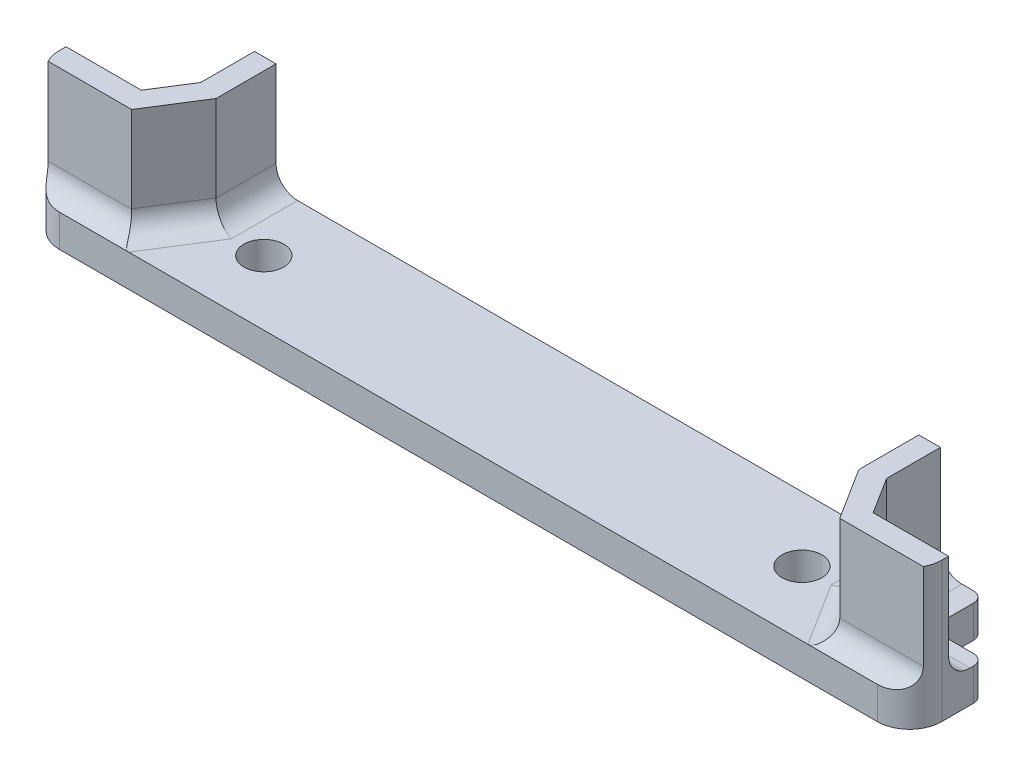
SolidWorks part; units mm, degrees
ref_plane "Front Plane" through (0, 0, 0) normal (0, 0, 1) x (1, 0, 0)
ref_plane "Top Plane" through (0, 0, 0) normal (0, 1, 0) x (1, 0, 0)
ref_plane "Right Plane" through (0, 0, 0) normal (1, 0, 0) x (0, 0, -1)
sketch "Sketch1" plane through (0, 0, 0) normal (0, 1, 0) x (1, 0, 0)
  line L1 (41, -6) -> (-41, -6)
  line L2 (41, -6) -> (41, 6)
  line L3 (41, 6) -> (-41, 6)
  line L4 (-41, -6) -> (-41, 6)
  line L5 (41, -6) -> (-41, 6) construction
  line L6 (41, 6) -> (-41, -6) construction
  point P0 (0, 0)
  dimension "D1" = 82
  dimension "D2" = 12
extrude "Boss-Extrude1" add sketch "Sketch1" along normal blind 3
sketch "Sketch2" plane through (0, 3, 0) normal (0, 1, 0) x (1, 0, 0)
  line L0 (-41, 0) -> (41, 0) construction
  line L1 (-41, 6) -> (-41, -6) construction
  line L2 (41, -6) -> (41, 6) construction
  circle A0 centre (-25, 0) radius 1.85
  circle A1 centre (25, 0) radius 1.85
  dimension "D1" = 3.7
  dimension "D2" = 3.7
  dimension "D3" = 25
  dimension "D4" = 50
extrude "Cut-Extrude1" cut sketch "Sketch2" against normal through all
fillet "Fillet1" radius 3 4 edges at (-41, 1.5, -6) (-41, 1.5, 6) (41, 1.5, 6) (41, 1.5, -6)
sketch "Sketch3" plane through (0, 3, 0) normal (0, 1, 0) x (1, 0, 0)
  line L0 (-31.864, 6) -> (-31.864, 1)
  line L1 (-42, -2.382) -> (-42, -4.382)
  line L2 (-31.864, 1) -> (-34, -2.382)
  line L3 (-34, -2.382) -> (-38, -2.382)
  line L4 (-29.864, 6) -> (-29.864, 0.4213)
  line L5 (-29.864, 0.4213) -> (-32.8977, -4.382)
  line L6 (-32.8977, -4.382) -> (-36.5542, -4.382)
  line L7 (-42, -4.382) -> (-37, -4.382)
  line L8 (-42, -2.382) -> (-38, -2.382)
  line L16 (-31.864, 6) -> (-29.864, 6)
  line L18 (-37, -4.382) -> (-36.314, -4.382)
  line L19 (-41, 3) -> (-41, -3) construction
  line L20 (-36.5542, -4.382) -> (-36.5542, -4.382) construction
  line L21 (-38, -2.382) -> (-38, -3) construction
  line M14 (38, 6) -> (-38, 6)
  line M16 (-41, 3) -> (-41, -3)
  arc M17 (-41, -3) -> (-38, -6) centre (-38, -3) ccw
  dimension "D2" = 5
  dimension "D4" = 4
  dimension "D7" = 11.136
  dimension "D1" = 5
  dimension "D5" = 2
extrude "Boss-Extrude2" add sketch "Sketch3" along normal blind 10 contours L18 L6 L5 L4 L0 L2 L3 M14 M16 M17 region at (-30.864, 3, -5.8478)
fillet "Fillet2" radius 2 6 edges at (-36.7802, 3, 4.382) (-29.864, 3, -3.2106) (-31.3808, 3, 1.9803) (-31.864, 3, -3.5) (-32.932, 3, 0.691) (-37.5, 3, 2.382)
sketch "Sketch4" plane through (0, 3, 0) normal (0, 1, 0) x (1, 0, 0)
  line L0 (-35.932, 6) -> (-35.932, 0.9483)
  line L1 (-33.864, 6) -> (-38, 6) construction
  line L2 (-35.932, 0.9483) -> (-41, 0.9483)
  line L3 (-41, 3) -> (-41, -0.382) construction
  line L9 (-35.1023, -0.382) -> (-33.864, 1.5787)
  line L10 (-33.864, 1.5787) -> (-33.864, 6)
  line L11 (-33.864, 6) -> (-38, 6)
  line L12 (-41, 3) -> (-41, -0.382)
  line L13 (-41, -0.382) -> (-35.1023, -0.382)
  line L16 (-35.932, 6) -> (-38, 6)
  line L17 (-41, 3) -> (-41, 0.9483)
  arc A2 (-38, 6) -> (-41, 3) centre (-38, 3) ccw
  arc A3 (-38, 6) -> (-41, 3) centre (-38, 3) ccw
  dimension "D1" = 0
extrude "Cut-Extrude3" cut sketch "Sketch4" against normal through all
fillet "Fillet3" radius 1 3 edges at (-35.932, 1.5, -6) (-41, 1.5, -0.9483) (-35.932, 1.5, -0.9483)
mirror "Mirror2" about plane through (0, 0, 0) normal (1, 0, 0) of "Cut-Extrude3", "Boss-Extrude2"
fillet "Fillet4" radius 2 6 edges at (29.864, 3, -3.2106) (36.7802, 3, 4.382) (31.3808, 3, 1.9803) (37.5, 3, 2.382) (32.932, 3, 0.691) (31.864, 3, -3.5)
fillet "Fillet5" radius 1 3 edges at (41, 1.5, -0.9483) (35.932, 1.5, -0.9483) (35.932, 1.5, -6)
